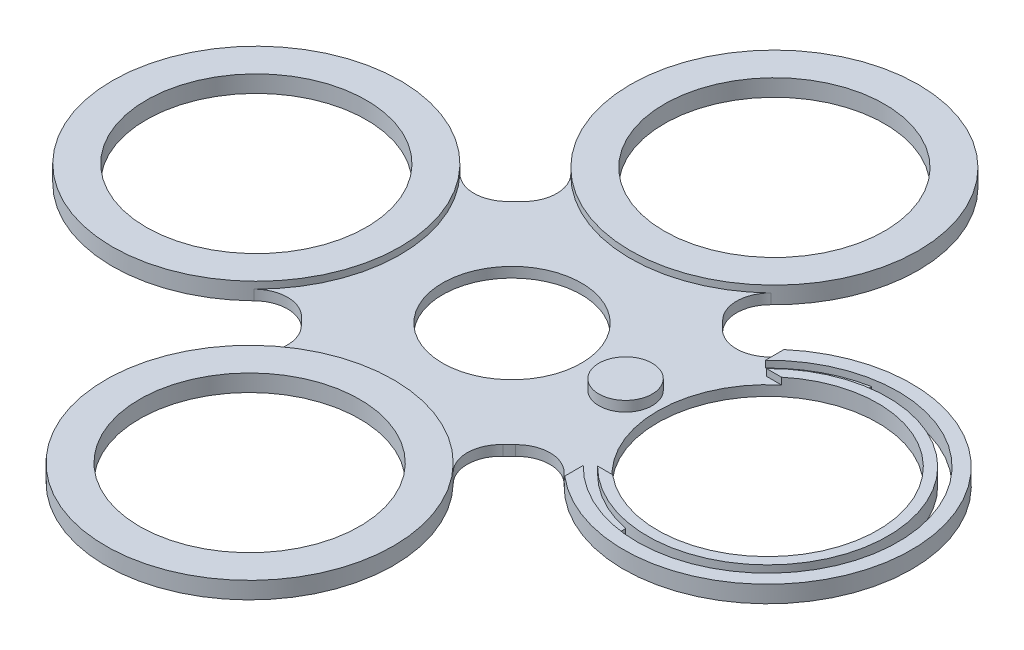
SolidWorks part; units mm, degrees
note: The reader was unsure of these and kept them because the rebuilt part matched: shared geometry of "Çizim1<3>", "Çizim3<4>", "Çizim3<6>".
ref_plane "Ön Düzlem" through (0, 0, 0) normal (0, 0, 1) x (1, 0, 0)
ref_plane "Üst Düzlem" through (0, 0, 0) normal (0, 1, 0) x (1, 0, 0)
ref_plane "Sağ Düzlem" through (0, 0, 0) normal (1, 0, 0) x (0, 0, -1)
sketch "Çizim1" plane through (0, 0, 0) normal (0, 1, 0) x (1, 0, 0)
  circle A0 centre (0, 0) radius 43.9658
  circle A1 centre (76.4593, -0.9924) radius 32.5
  circle A2 centre (-0.9924, -76.4593) radius 32.5
  circle A3 centre (-76.4593, 0.9924) radius 32.5
  circle A4 centre (0.9924, 76.4593) radius 32.5
  point P14 (0, 0)
  dimension "D2" = 65
  dimension "D1" = 4
extrude "Yükseklik-Ekstrüzyon1" add sketch "Çizim1" along normal blind 3 contours A0
extrude "Ekstrüzyon-İnce1" add sketch "Çizim1<3>" along normal blind 5 thin contours A3 | A2 | A1 | A4
sketch "Çizim1<3>" plane through (0, 0, 0) normal (0, 1, 0) x (1, 0, 0) same geometry as "Çizim1"
fillet "Radyus1" radius 10 8 edges at (-20.684, 1.5, 38.7965) (19.67, 1.5, 39.3202) (-38.7965, 1.5, -20.684) (-39.3202, 1.5, 19.67) (38.7965, 1.5, 20.684) (39.3202, 1.5, -19.67) (20.684, 1.5, -38.7965) (-19.67, 1.5, -39.3202)
sketch "Çizim3" plane through (0, 3, 0) normal (0, 1, 0) x (1, 0, 0)
  line L2 (69.3271, 36.8412) -> (69.3271, 33.7837)
  line L3 (69.3271, -35.7686) -> (69.3271, -38.826)
  line L4 (47.4224, 24.2881) -> (49.685, 22.3182)
  line L5 (47.2155, -26.0334) -> (49.4943, -24.0821)
  circle A0 centre (33.9629, -0.4408) radius 7.8781
  arc A1 (46.7266, 29.3756) -> (45.9484, -30.5785) centre (76.4593, -0.9924) ccw construction
  arc A8 (49.4943, -24.0821) -> (49.685, 22.3182) centre (76.4593, -0.9924) ccw
  arc A12 (47.2155, -26.0334) -> (47.4224, 24.2881) centre (76.4593, -0.9924) ccw
  arc A19 (69.3271, -35.7686) -> (69.3271, 33.7837) centre (76.4593, -0.9924) ccw
  arc A20 (69.3271, -38.826) -> (69.3271, 36.8412) centre (76.4593, -0.9924) ccw
  arc M9 (45.9484, -30.5785) -> (46.7266, 29.3756) centre (76.4593, -0.9924) cw
extrude "Kes-Ekstrüzyon1" cut sketch "Çizim3" against normal through all both and the other way through all contours L2 A19 L3 A20
sketch "Çizim4" plane through (0, 5, 0) normal (0, 1, 0) x (1, 0, 0)
  line L0 (48.9094, -25.9221) -> (55.6084, -25.9221)
  line L1 (27.961, 23.9372) -> (36.2829, 23.9372)
  line L2 (27.961, 23.9372) -> (27.961, -25.9221)
  line L3 (27.961, -25.9221) -> (36.2829, -25.9221)
  line L4 (55.6084, 23.9372) -> (55.6084, -25.9221)
  line L5 (36.2829, 40.2942) -> (48.9094, 40.2942)
  line L6 (36.2829, 40.2942) -> (36.2829, 23.9372)
  line L8 (48.9094, 40.2942) -> (48.9094, 23.9372)
  line L10 (48.9094, -25.9221) -> (48.9094, -39.1951)
  line L11 (48.9094, -39.1951) -> (36.2829, -39.1951)
  line L12 (36.2829, -25.9221) -> (36.2829, -39.1951)
  line L13 (48.9094, 23.9372) -> (55.6084, 23.9372)
  circle A0 centre (76.4593, -0.9924) radius 32.5 construction
extrude "Kes-Ekstrüzyon2" cut sketch "Çizim4" against normal up to surface (2 mm away) up to face at (0, 3, 0)
extrude "Kes-Ekstrüzyon3" cut sketch "Çizim3<4>" along normal through all contours L5 A12 L3 A8 | L2 A12 L4 A8
sketch "Çizim3<4>" plane through (0, 3, 0) normal (0, 1, 0) x (1, 0, 0) same geometry as "Çizim3"
sketch "Çizim6" plane through (0, 3, 0) normal (0, 1, 0) x (1, 0, 0)
  circle A0 centre (0, 0) radius 20.5
  dimension "D1" = 41
extrude "Kes-Ekstrüzyon4" cut sketch "Çizim6" against normal through all
extrude "Yükseklik-Ekstrüzyon4" add sketch "Çizim3<6>" along normal blind 3 contours A0 M9 | A0 M9
sketch "Çizim3<6>" plane through (0, 3, 0) normal (0, 1, 0) x (1, 0, 0) same geometry as "Çizim3"
